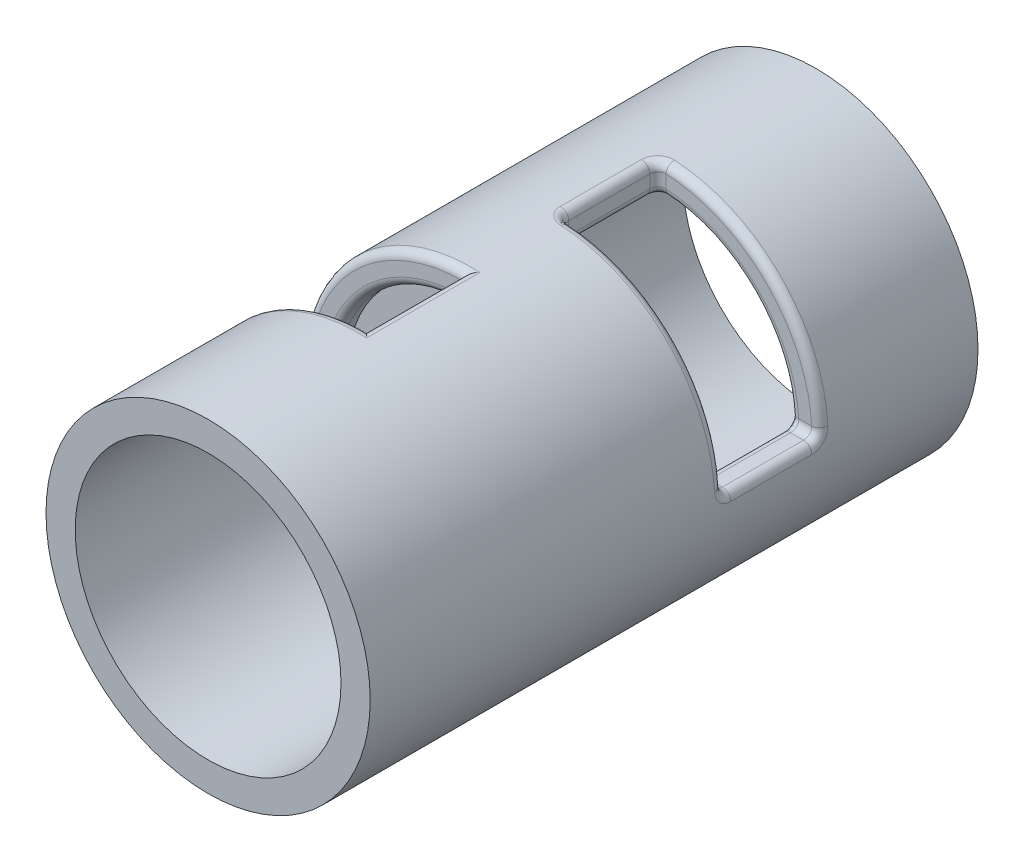
SolidWorks part; units mm, degrees
ref_plane "前视基准面" through (0, 0, 0) normal (0, 0, 1) x (1, 0, 0)
ref_plane "上视基准面" through (0, 0, 0) normal (0, 1, 0) x (1, 0, 0)
ref_plane "右视基准面" through (0, 0, 0) normal (1, 0, 0) x (0, 0, -1)
other "Configuration Table"
sketch "草图1" plane through (0, 0, 0) normal (0, 0, 1) x (1, 0, 0)
  circle A0 centre (0, 0) radius 20
  dimension "D1" = 40
extrude "凸台-拉伸1" add sketch "草图1" along normal blind 75
sketch "草图2" plane through (0, 0, 75) normal (0, 0, 1) x (1, 0, 0)
  circle A0 centre (0, 0) radius 16.4
  dimension "D1" = 32.8
extrude "切除-拉伸1" cut sketch "草图2" against normal blind 33.6
sketch "草图3" plane through (0, 0, 0) normal (0, 0, -1) x (-1, 0, 0)
  circle A0 centre (0, 0) radius 16.4
  dimension "D1" = 32.8
extrude "切除-拉伸2" cut sketch "草图3" against normal blind 33.5
ref_plane "基准面1" through (0, 0, 37.5) normal (0, 0, 1) x (1, 0, 0)
sketch "草图8" plane through (0, 0, 37.5) normal (0, 0, 1) x (1, 0, 0)
  line L2 (0, -20) -> (0, 20)
  line L3 (-20, 0) -> (20, 0)
  circle A0 centre (0, 0) radius 20
  circle A1 centre (0, 0) radius 10
  dimension "D1" = 40
  dimension "D2" = 20
extrude "切除-拉伸4" cut sketch "草图8" along normal blind 12 from offset 6 contours A1 L2 A0 L3 region at (-9.903, 9.903, 37.5)
extrude "切除-拉伸6" cut sketch "草图8<5>" against normal blind 12 from offset 6 contours A1 L3 A0 L2 region at (9.903, 9.903, 37.5) offset against normal yes
sketch "草图8<5>" plane through (0, 0, 37.5) normal (0, 0, 1) x (1, 0, 0) same geometry as "草图8"
fillet "圆角1" radius 1 21 edges at (0, 16.4, 25.5) (0, 20, 25.5) (20, 0, 25.5) (16.4, 0, 25.5) (-14.1421, 14.1421, 55.5) (-11.5966, 11.5966, 55.5) (-11.5966, 11.5966, 43.5) (11.5966, 11.5966, 31.5) (18.2, 0, 31.5) (14.1421, 14.1421, 31.5) (0, 18.2, 31.5) (0, 18.2, 19.5) (14.1421, 14.1421, 19.5) (18.2, 0, 19.5) (11.5966, 11.5966, 19.5) (-18.2, 0, 55.5) (-20, 0, 49.5) (-18.2, 0, 43.5) (-16.4, 0, 49.5) (0, 20, 49.5) (-14.1421, 14.1421, 43.5)
